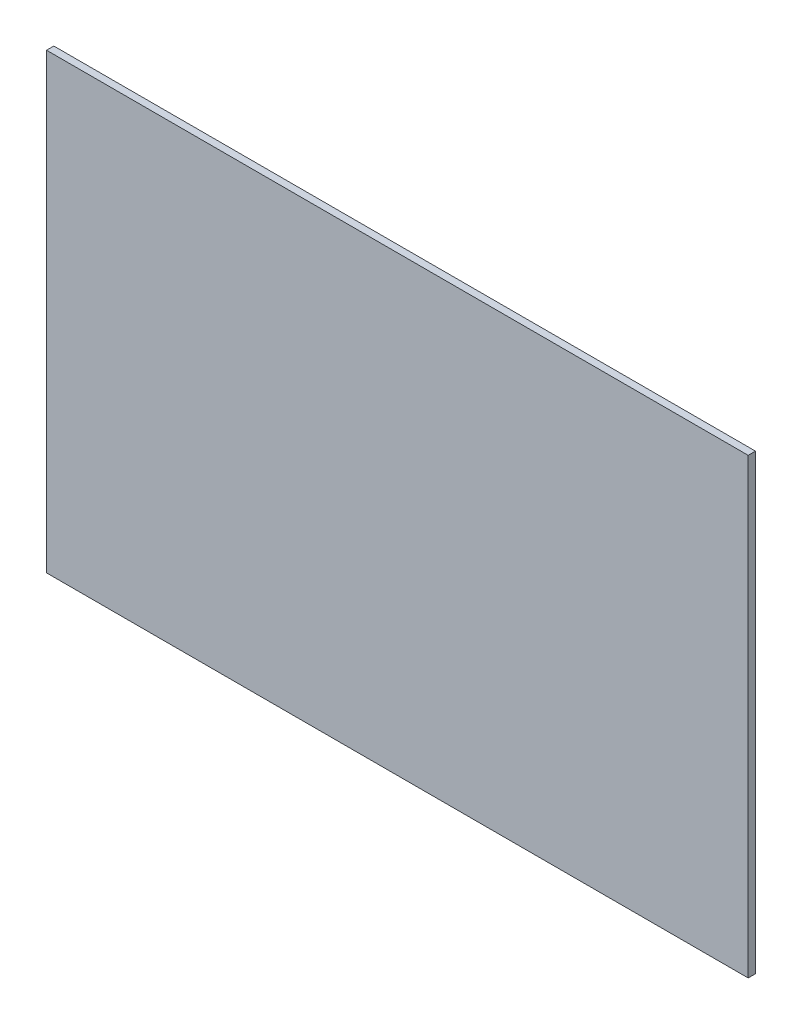
SolidWorks part; units mm, degrees
material "ABS"
ref_plane "X-Y Datum" through (0, 0, 0) normal (0, 0, 1) x (1, 0, 0)
ref_plane "X-Z Datum" through (0, 0, 0) normal (0, 1, 0) x (1, 0, 0)
ref_plane "Y-Z Datum" through (0, 0, 0) normal (1, 0, 0) x (0, 0, -1)
sketch "Sketch1" plane through (0, 0, 0) normal (0, 0, 1) x (1, 0, 0)
  line L0 (-153.025, 98.7125) -> (-153.025, -98.7125)
  line L1 (-153.025, 98.7125) -> (153.025, 98.7125)
  line L2 (-153.025, 98.7125) -> (-153.025, -98.7125)
  line L3 (-153.025, -98.7125) -> (153.025, -98.7125)
  line L4 (153.025, 98.7125) -> (153.025, -98.7125)
  line L5 (-153.025, 98.7125) -> (153.025, -98.7125) construction
  line L6 (-153.025, -98.7125) -> (153.025, 98.7125) construction
  line L7 (-153.025, -98.7125) -> (153.025, -98.7125)
  line L8 (153.025, 98.7125) -> (153.025, -98.7125)
  line L9 (-153.025, 98.7125) -> (153.025, 98.7125)
  circle A0 centre (-142.25, -87.9375) radius 10.775
  circle A1 centre (-118.25, -87.9375) radius 10.775 construction
  circle A2 centre (-130.25, -64.9375) radius 10.775
  point P0 (0, 0)
  dimension "D1" = 21.55
  dimension "D2" = 24
  dimension "D3" = 23
  dimension "D4" = 12
  dimension "D5" = 197.425
  dimension "D6" = 306.05
  dimension "D7" = 0
extrude "Boss-Extrude1" add sketch "Sketch1" along normal blind 3.175 contours A0 L3 L4 L1 L2 A2 | A2 | A0 | A0 L2 L3 | L9 L0 L7 L8 L1 L4 L3 L2 region at (1.7287, 0.9747, 0) region at (-150.6182, -96.3057, 0) region at (-142.25, -87.9375, 0) region at (-130.25, -64.9375, 0)
